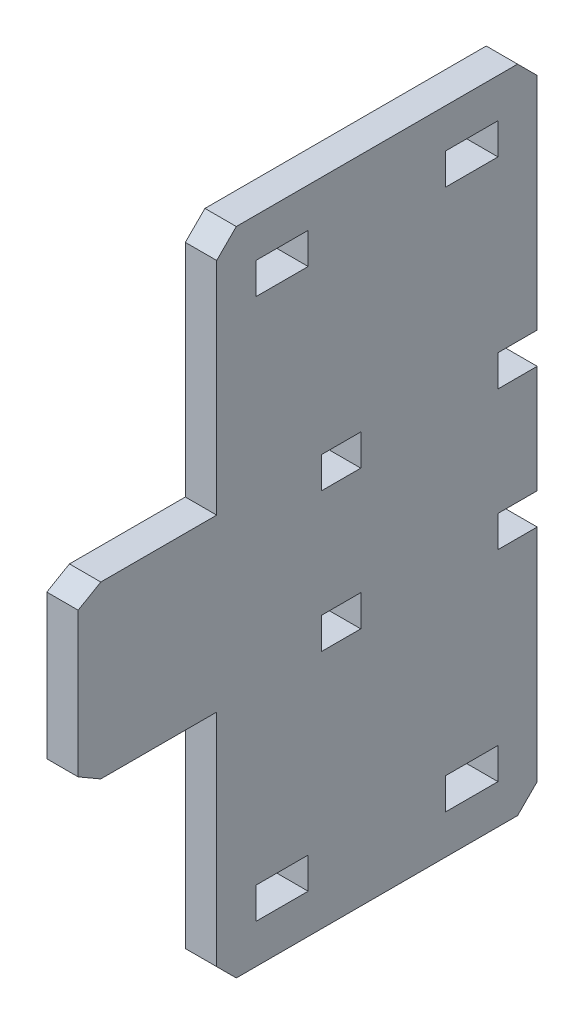
SolidWorks part; units mm, degrees
ref_plane "Front" through (0, 0, 0) normal (0, 0, 1) x (1, 0, 0)
ref_plane "Top" through (0, 0, 0) normal (0, 1, 0) x (1, 0, 0)
ref_plane "Right" through (0, 0, 0) normal (1, 0, 0) x (0, 0, -1)
ref_axis "side-side" through (80.9, 0, 0) along (-1, 0, 0)
ref_axis "up-down" through (0, 50, 0) along (0, -1, 0)
ref_axis "front-back" through (0, 0, -80.9) along (0, 0, 1)
sketch "Sketch1" plane through (0, 0, 0) normal (1, 0, 0) x (0, 0, -1)
  line L0 (27.94, 55.626) -> (27.94, 49.53) construction
  line L1 (38.1, -49.53) -> (27.94, -49.53)
  line L2 (45.72, -63.246) -> (45.72, -16.5735)
  line L3 (38.1, 49.53) -> (27.94, 49.53)
  line L4 (-43.4959, -14.0335) -> (-43.4959, 14.0335)
  line L5 (109.3291, 0) -> (45.72, 0) construction
  line L6 (1.2081, 55.626) -> (1.2081, 49.53) construction
  line L7 (27.94, 55.626) -> (27.94, 49.53)
  line L8 (45.72, -54.61) -> (38.1, -54.61) construction
  line L9 (38.1, 49.53) -> (38.1, 55.626)
  line L10 (38.1, 54.61) -> (45.72, 54.61) construction
  line L12 (-16.5719, 54.61) -> (-8.9519, 54.61) construction
  line L13 (38.1, 16.5735) -> (45.72, 16.5735)
  line L14 (38.1, -55.626) -> (38.1, -49.53)
  line L15 (-8.9519, 55.626) -> (-8.9519, 49.53)
  line L16 (-16.5719, -54.61) -> (-8.9519, -54.61) construction
  line L17 (38.1, 16.5735) -> (38.1, 10.4775)
  line L18 (38.1, 10.4775) -> (45.72, 10.4775)
  line L19 (-8.9519, -55.626) -> (-8.9519, -49.53)
  line L20 (45.72, 16.5735) -> (45.72, 63.246)
  line L21 (38.1, -10.4775) -> (45.72, -10.4775)
  line L22 (38.1, -10.4775) -> (38.1, -16.5735)
  line L23 (38.1, -16.5735) -> (45.72, -16.5735)
  line L24 (1.2081, 55.626) -> (1.2081, 49.53)
  line L25 (11.43, 16.5735) -> (3.81, 16.5735)
  line L26 (11.43, 16.5735) -> (11.43, 10.4775)
  line L27 (11.43, 10.4775) -> (3.81, 10.4775)
  line L28 (3.81, 16.5735) -> (3.81, 10.4775)
  line L29 (3.81, -16.5735) -> (11.43, -16.5735)
  line L30 (3.81, -16.5735) -> (3.81, -10.4775)
  line L31 (3.81, -10.4775) -> (11.43, -10.4775)
  line L32 (11.43, -16.5735) -> (11.43, -10.4775)
  line L34 (45.72, -10.4775) -> (45.72, 10.4775)
  line L35 (-16.5719, 63.246) -> (-16.5719, 16.5735)
  line L36 (-16.5719, -63.246) -> (-16.5719, -16.5735)
  line L37 (-16.5719, 16.5735) -> (-39.0964, 16.5735)
  line L38 (-16.5719, -16.5735) -> (-39.0964, -16.5735)
  line L39 (-39.0964, 16.5735) -> (-43.4959, 14.0335)
  line L40 (-39.0964, -16.5735) -> (-43.4959, -14.0335)
  line L41 (45.72, 63.246) -> (-16.5719, 63.246)
  line L43 (38.1, 55.626) -> (27.94, 55.626)
  line L45 (38.1, -55.626) -> (27.94, -55.626)
  line L46 (45.72, -63.246) -> (-16.5719, -63.246)
  line L47 (1.2081, 55.626) -> (-8.9519, 55.626)
  line L48 (1.2081, 49.53) -> (-8.9519, 49.53)
  line L49 (27.94, -49.53) -> (27.94, -55.626) construction
  line L50 (1.2081, -49.53) -> (1.2081, -55.626) construction
  line L51 (27.94, -49.53) -> (27.94, -55.626)
  line L52 (1.2081, -49.53) -> (1.2081, -55.626)
  line L53 (1.2081, -49.53) -> (-8.9519, -49.53)
  line L54 (1.2081, -55.626) -> (-8.9519, -55.626)
extrude "Boss-Extrude1" add sketch "Sketch1" along normal mid plane 6.096
chamfer "Chamfer2" distance 3.81 angle 45 4 edges at (0, -63.246, -45.72) (0, -63.246, 16.5719) (0, 63.246, -45.72) (0, 63.246, 16.5719)
